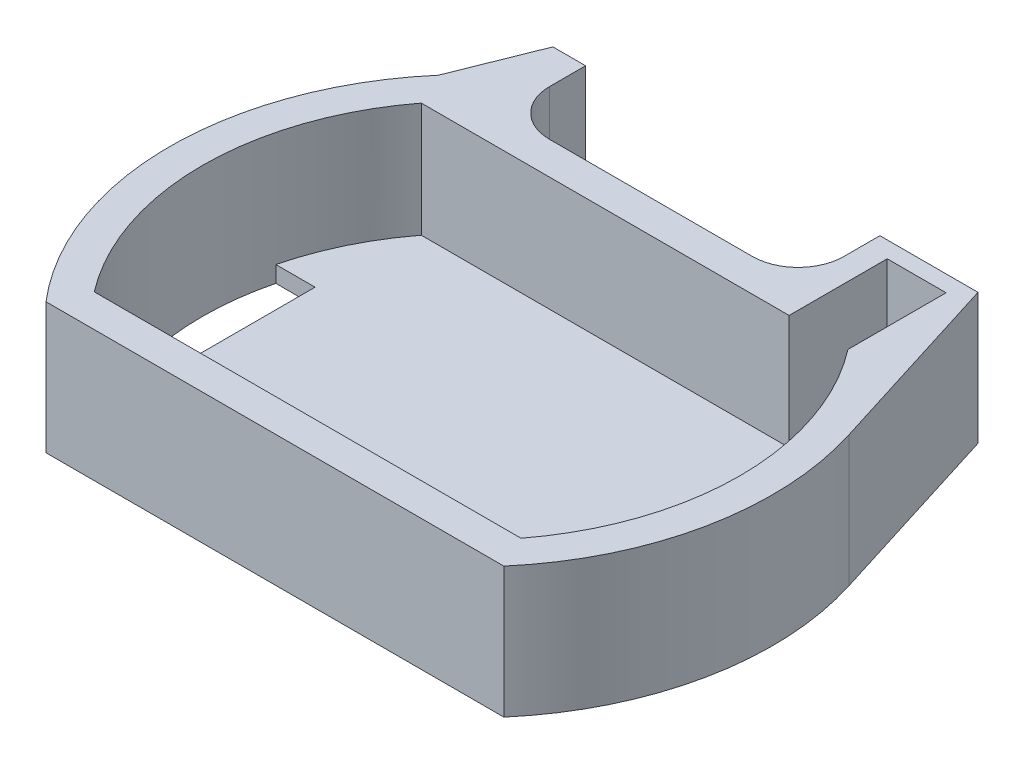
SolidWorks part; units mm, degrees
material "TPU Ultimaker"
ref_plane "Front Plane" through (0, 0, 0) normal (0, 0, 1) x (1, 0, 0)
ref_plane "Top Plane" through (0, 0, 0) normal (0, 1, 0) x (1, 0, 0)
ref_plane "Right Plane" through (0, 0, 0) normal (1, 0, 0) x (0, 0, -1)
sketch "Sketch1" plane through (0, 0, 0) normal (0, 1, 0) x (1, 0, 0)
  line L0 (0, 76.2) -> (0, -76.2) construction
  line L1 (-88.9, -76.2) -> (88.9, -76.2)
  line L5 (-88.9, -76.2) -> (88.9, 76.2) construction
  line L6 (-88.9, 76.2) -> (88.9, -76.2) construction
  line L15 (-101.2509, 25.4) -> (-86.0109, 25.4)
  line L17 (-86.0109, 25.4) -> (-86.0109, -25.4)
  line L19 (-86.0109, -25.4) -> (-101.2509, -25.4)
  line L24 (0, 59.6666) -> (44.45, 59.6666) construction
  line L25 (0, 59.6666) -> (0, 27.9166) construction
  line L26 (0, 27.9166) -> (44.45, 27.9166) construction
  line L27 (44.45, 59.6666) -> (44.45, 27.9166) construction
  line L28 (86.0109, -25.4) -> (101.2509, -25.4)
  line L29 (86.0109, 25.4) -> (86.0109, -25.4)
  line L30 (101.2509, 25.4) -> (86.0109, 25.4)
  line L32 (15.7788, 14.5728) -> (96.7788, 14.5728) construction
  line L33 (15.7788, 14.5728) -> (15.7788, -10.4272) construction
  line L34 (15.7788, -10.4272) -> (96.7788, -10.4272) construction
  line L35 (96.7788, 14.5728) -> (96.7788, -10.4272) construction
  line L36 (-98.2629, 14.5728) -> (-17.2629, 14.5728) construction
  line L37 (-98.2629, 14.5728) -> (-98.2629, -10.4272) construction
  line L38 (-98.2629, -10.4272) -> (-17.2629, -10.4272) construction
  line L39 (-17.2629, 14.5728) -> (-17.2629, -10.4272) construction
  line L41 (-33.8081, -17.729) -> (34.1919, -17.729) construction
  line L42 (-33.8081, -17.729) -> (-33.8081, -52.729) construction
  line L43 (-33.8081, -52.729) -> (34.1919, -52.729) construction
  line L44 (34.1919, -17.729) -> (34.1919, -52.729) construction
  line L45 (-63.5, 107.95) -> (-63.5, 76.2)
  line L47 (63.5, 107.95) -> (63.5, 76.2)
  line L48 (-63.5, 76.2) -> (63.5, 76.2)
  line L49 (-88.9, 76.2) -> (-76.2, 107.95)
  line L50 (-76.2, 107.95) -> (-63.5, 107.95)
  line L51 (88.9, 107.95) -> (63.5, 107.95)
  line L53 (111.7418, 34.9773) -> (88.9, 107.95)
  arc A0 (-88.9, 76.2) -> (-88.9, -76.2) centre (0, 0) ccw
  arc A4 (-101.2509, 25.4) -> (-101.2509, -25.4) centre (0, 0) ccw
  arc A5 (-79.2574, 67.9349) -> (-79.2574, -67.9349) centre (0, 0) ccw construction
  arc A6 (101.2509, 25.4) -> (101.2509, -25.4) centre (0, 0) cw
  arc A7 (111.7418, 34.9773) -> (88.9, -76.2) centre (0, 0) cw
  point P0 (0, 0)
  point P46 (117.0882, 0)
  dimension "D1" = 177.8
  dimension "D2" = 12.7
  dimension "D3" = 152.4
  dimension "D4" = 31.75
  dimension "D5" = 44.45
  dimension "D6" = 50.8
  dimension "D7" = 15.24
  dimension "D8" = 81
  dimension "D9" = 25
  dimension "D10" = 81
  dimension "D11" = 25
  dimension "D12" = 35
  dimension "D13" = 68
  dimension "D14" = 12.7
  dimension "D15" = 127
  dimension "D16" = 31.75
  dimension "D17" = 25.4
extrude "Boss-Extrude1" add sketch "Sketch1" along normal blind 6.35
sketch "Sketch2" plane through (0, 6.35, 0) normal (0, 1, 0) x (1, 0, 0)
  line L5 (-88.9, -76.2) -> (88.9, -76.2) construction
  line L11 (-88.9, -76.2) -> (88.9, -76.2)
  line L15 (63.5, 107.95) -> (63.5, 76.2) construction
  line L17 (-63.5, 76.2) -> (-63.5, 107.95) construction
  line L18 (63.5, 76.2) -> (-63.5, 76.2) construction
  line L20 (63.5, 107.95) -> (63.5, 76.2)
  line L22 (-63.5, 76.2) -> (-63.5, 107.95)
  line L23 (63.5, 76.2) -> (-63.5, 76.2)
  line L28 (-82.8532, -63.5) -> (82.8532, -63.5)
  line L29 (-88.9, -63.5) -> (88.9, -63.5) construction
  line L30 (-82.8532, 63.5) -> (82.8532, 63.5)
  line L32 (88.9, 107.95) -> (63.5, 107.95) construction
  line L33 (-63.5, 107.95) -> (-76.2, 107.95) construction
  line L34 (-76.2, 107.95) -> (-88.9, 76.2) construction
  line L36 (88.9, 107.95) -> (63.5, 107.95)
  line L37 (-63.5, 107.95) -> (-76.2, 107.95)
  line L38 (-76.2, 107.95) -> (-88.9, 76.2)
  line L39 (111.7418, 34.9773) -> (88.9, 107.95) construction
  line L40 (111.7418, 34.9773) -> (88.9, 107.95)
  arc A26 (-82.8532, 63.5) -> (-82.8532, -63.5) centre (0, 0) ccw
  arc A27 (82.8532, -63.5) -> (82.8532, 63.5) centre (0, 0) ccw
  arc A29 (-88.9, 76.2) -> (-88.9, -76.2) centre (0, 0) ccw construction
  arc A31 (-88.9, 76.2) -> (-88.9, -76.2) centre (0, 0) ccw
  arc A32 (88.9, -76.2) -> (111.7418, 34.9773) centre (0, 0) ccw construction
  arc A33 (88.9, -76.2) -> (111.7418, 34.9773) centre (0, 0) ccw
  dimension "D3" = 12.7
  dimension "D1" = 12.7
extrude "Boss-Extrude2" add sketch "Sketch2" along normal blind 44.45
sketch "Sketch4" plane through (0, 50.8, 0) normal (0, 1, 0) x (1, 0, 0)
  line L0 (63.5, 107.95) -> (50.8, 107.95)
  line L1 (50.8, 107.95) -> (50.8, 76.2)
  line L2 (63.5, 76.2) -> (-63.5, 76.2) construction
  line L3 (50.8, 76.2) -> (63.5, 76.2)
  line L4 (63.5, 76.2) -> (63.5, 107.95)
  line L5 (-63.5, 76.2) -> (-63.5, 107.95) construction
  dimension "D1" = 114.3
extrude "Boss-Extrude4" add sketch "Sketch4" against normal up to surface (50.8 mm away) up to face at (-94.4152, 0, 0)
sketch "Sketch5" plane through (0, 50.8, 0) normal (0, 1, 0) x (1, 0, 0)
  line L0 (59.9932, 63.5) -> (59.9932, 101.6)
  line L1 (82.8532, 63.5) -> (-82.8532, 63.5) construction
  line L2 (59.9932, 101.6) -> (82.8532, 101.6)
  line L3 (82.8532, 63.5) -> (82.8532, 101.6)
  line L5 (50.8, 76.2) -> (-63.5, 76.2) construction
  line L6 (59.9932, 63.5) -> (82.8532, 63.5)
  dimension "D1" = 25.4
  dimension "D2" = 22.86
extrude "Cut-Extrude1" cut sketch "Sketch5" against normal up to surface (44.45 mm away) up to face at (0, 6.35, 0)
fillet "Fillet3" radius 17.78 2 edges at (50.8, 25.4, -76.2) (-63.5, 25.4, -76.2)
ref_plane "Plane1" through (57.15, 0, 0) normal (1, 0, 0) x (0, 0, -1)
